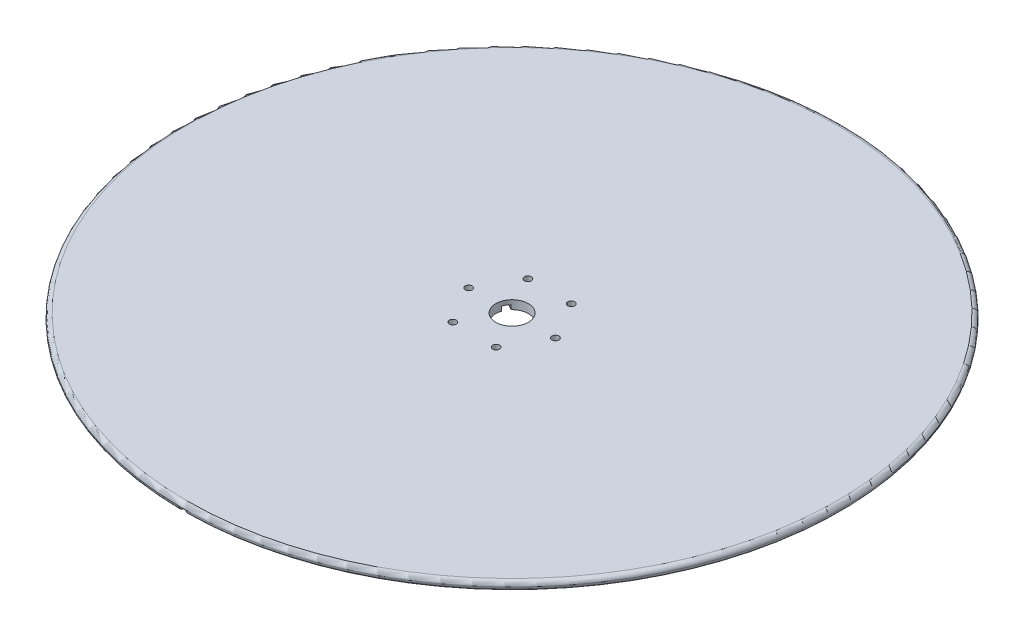
SolidWorks part; units mm, degrees
material "6061-T6 (SS)"
ref_plane "Alzado" through (0, 0, 0) normal (0, 0, 1) x (1, 0, 0)
ref_plane "Planta" through (0, 0, 0) normal (0, 1, 0) x (1, 0, 0)
ref_plane "Vista lateral" through (0, 0, 0) normal (1, 0, 0) x (0, 0, -1)
sketch "Croquis1" plane through (0, 0, 0) normal (0, 1, 0) x (1, 0, 0)
  circle A0 centre (0, 0) radius 380
  circle A1 centre (0, 0) radius 18.75
  dimension "D1" = 760
  dimension "D2" = 37.5
extrude "Saliente-Extruir1" add sketch "Croquis1" along normal blind 10
sketch "Croquis2" plane through (0, 10, 0) normal (0, 1, 0) x (1, 0, 0)
  line L0 (0, 0) -> (-329.0897, -190) construction
  line L1 (50, 0) -> (25, 43.3013) construction
  line L2 (25, 43.3013) -> (-25, 43.3013) construction
  line L3 (-25, 43.3013) -> (-50, 0) construction
  line L4 (-50, 0) -> (-25, -43.3013) construction
  line L5 (-25, -43.3013) -> (25, -43.3013) construction
  line L6 (25, -43.3013) -> (50, 0) construction
  line L7 (0, 0) -> (329.0897, -190) construction
  line L8 (0, 0) -> (0, 380) construction
  line L9 (0, 0) -> (-25, -43.3013) construction
  circle A0 centre (0, 0) radius 43.3013 construction
  circle A1 centre (0, 0) radius 380 construction
  circle A2 centre (-25, -43.3013) radius 4
  circle A3 centre (-50, 0) radius 4
  circle A4 centre (-25, 43.3013) radius 4
  circle A5 centre (25, 43.3013) radius 4
  circle A6 centre (50, 0) radius 4
  circle A7 centre (25, -43.3013) radius 4
  dimension "D4" = 8
  dimension "D5" = 6
  dimension "D1" = 50
  dimension "D2" = 120
  dimension "D3" = 120
  dimension "D6" = 50
extrude "Cortar-Extruir1" cut sketch "Croquis2" against normal through all
fillet "Redondeo1" radius 5 2 edges at (0, 0, 380) (0, 10, 380)
sketch "Croquis3" plane through (0, 0, 0) normal (0, -1, 0) x (-1, 0, 0)
  line L0 (0, 0) -> (0, -380) construction
  line L1 (4, 0) -> (4, -380)
  line L2 (-4, 0) -> (-4, -380)
  line L3 (0, 0) -> (-329.0897, 190) construction
  line L4 (-2, -3.4641) -> (-331.0897, 186.5359)
  line L5 (2, 3.4641) -> (-327.0897, 193.4641)
  line L6 (0, 0) -> (329.0897, 190) construction
  line L7 (-2, 3.4641) -> (327.0897, 193.4641)
  line L8 (2, -3.4641) -> (331.0897, 186.5359)
  circle A0 centre (0, 0) radius 380 construction
  arc A1 (4, 0) -> (-4, 0) centre (0, 0) ccw
  arc A2 (-4, -380) -> (4, -380) centre (0, -380) ccw
  arc A3 (-2, -3.4641) -> (2, 3.4641) centre (0, 0) ccw
  arc A4 (-327.0897, 193.4641) -> (-331.0897, 186.5359) centre (-329.0897, 190) ccw
  arc A5 (-2, 3.4641) -> (2, -3.4641) centre (0, 0) ccw
  arc A6 (331.0897, 186.5359) -> (327.0897, 193.4641) centre (329.0897, 190) ccw
  point P6 (0, -190)
  point P13 (-164.5448, 95)
  point P18 (164.5448, 95)
  dimension "D1" = 8
  dimension "D2" = 120
  dimension "D3" = 120
  dimension "D4" = 8
  dimension "D5" = 8
extrude "Cortar-Extruir2" cut sketch "Croquis3" against normal blind 5 contours L8 A6 L7 A5 | L2 A2 L1 A1 | L4 A4 L5 A3
